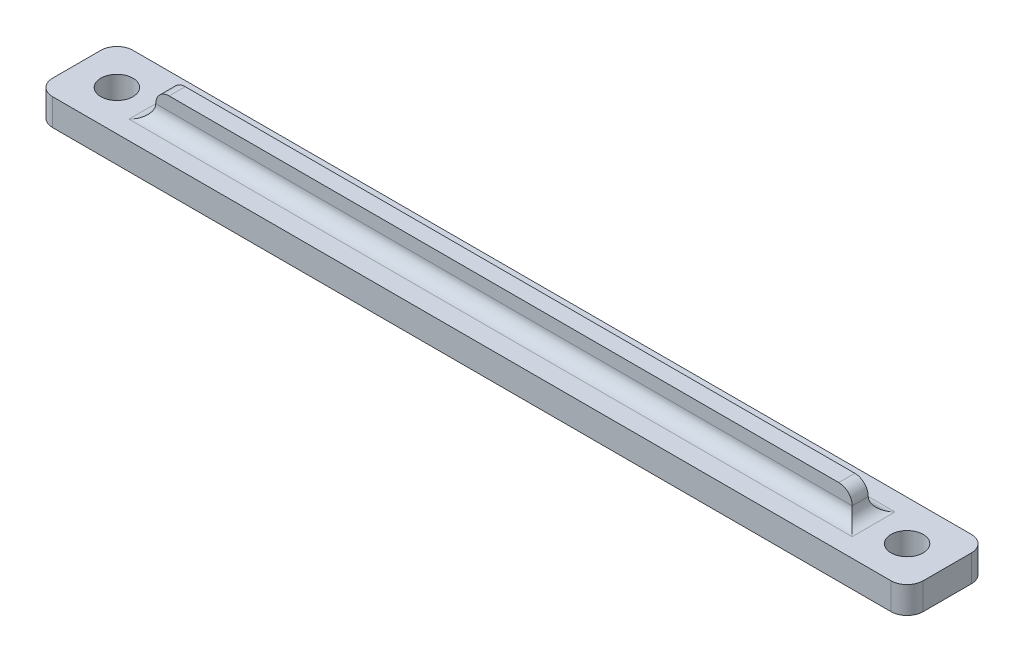
SolidWorks part; units mm, degrees
ref_plane "Front Plane" through (0, 0, 0) normal (0, 0, 1) x (1, 0, 0)
ref_plane "Top Plane" through (0, 0, 0) normal (0, 1, 0) x (1, 0, 0)
ref_plane "Right Plane" through (0, 0, 0) normal (1, 0, 0) x (0, 0, -1)
sketch "Sketch1" plane through (0, 0, 0) normal (0, 1, 0) x (1, 0, 0)
  line L1 (0, 0) -> (65, 0)
  line L2 (0, 0) -> (0, -6)
  line L3 (0, -6) -> (65, -6)
  line L4 (65, 0) -> (65, -6)
  dimension "D1" = 65
  dimension "D2" = 6
extrude "Boss-Extrude1" add sketch "Sketch1" along normal blind 2
sketch "Sketch2" plane through (0, 2, 0) normal (0, 1, 0) x (1, 0, 0)
  line L0 (0, -6) -> (65, -6) construction
  line L1 (0, 0) -> (0, -6) construction
  circle A0 centre (62, -3) radius 1.2
  circle A1 centre (3, -3) radius 1.2
  point P6 (0, 0)
  point P7 (0, 0)
  point P8 (60.4184, -3.3127)
  dimension "D1" = 2.4
  dimension "D2" = 2.4
  dimension "D3" = 3
  dimension "D4" = 59
  dimension "D5" = 3
extrude "Cut-Extrude1" cut sketch "Sketch2" against normal through all
sketch "Sketch3" plane through (0, 2, 0) normal (0, 1, 0) x (1, 0, 0)
  line L0 (0, -6) -> (65, -6) construction
  line L1 (6.5, -2.4) -> (58.5, -2.4)
  line L2 (6.5, -2.4) -> (6.5, -3.6)
  line L3 (6.5, -3.6) -> (58.5, -3.6)
  line L4 (58.5, -2.4) -> (58.5, -3.6)
  line L5 (65, -6) -> (65, 0) construction
  dimension "D1" = 1.2
  dimension "D2" = 52
  dimension "D4" = 2.4
  dimension "D3" = 6.5
extrude "Boss-Extrude2" add sketch "Sketch3" along normal blind 2
fillet "Fillet1" radius 1.2 4 edges at (0, 1, 6) (0, 1, 0) (65, 1, 0) (65, 1, 6)
fillet "Fillet3" radius 1 2 edges at (58.5, 4, 3) (6.5, 4, 3)
fillet "Fillet4" radius 1 2 edges at (32.5, 2, 3.6) (32.5, 2, 2.4)
fillet "Fillet5" radius 1 2 edges at (58.5, 2, 3) (6.5, 2, 3)
sketch "Sketch4" plane through (0, 0, 0) normal (0, -1, 0) x (-1, 0, 0)
  line L0 (-1.2, -6) -> (-63.8, -6) construction
  line L1 (-65, -4.8) -> (-65, -1.2) construction
  line L2 (0, -1.2) -> (0, -4.8) construction
  circle A0 centre (-20, -3) radius 2.15
  circle A1 centre (-45, -3) radius 2.15
  circle A2 centre (-20, -3) radius 1.55
  circle A3 centre (-45, -3) radius 1.55
  dimension "D3" = 3
  dimension "D1" = 4.3
  dimension "D2" = 4.3
  dimension "D4" = 3
  dimension "D5" = 20
  dimension "D6" = 20
  dimension "D7" = 0.6
  dimension "D8" = 0.6
extrude "Cut-Extrude2" cut sketch "Sketch4" against normal blind 0.8
equation "\"D3@Sketch2\"=\"D2@Sketch1\"/2"
equation "\"D5@Sketch2\"=\"D1@Sketch1\"/2-\"D4@Sketch2\"/2"
equation "\"D4@Sketch3\"=\"D2@Sketch1\"/2-\"D1@Sketch3\"/2"
equation "\"D3@Sketch4\"=\"D2@Sketch1\"/2"
equation "\"D4@Sketch4\"=\"D2@Sketch1\"/2"
equation "\"D3@Sketch3\"=(\"D1@Sketch1\"-\"D2@Sketch3\")/2"
